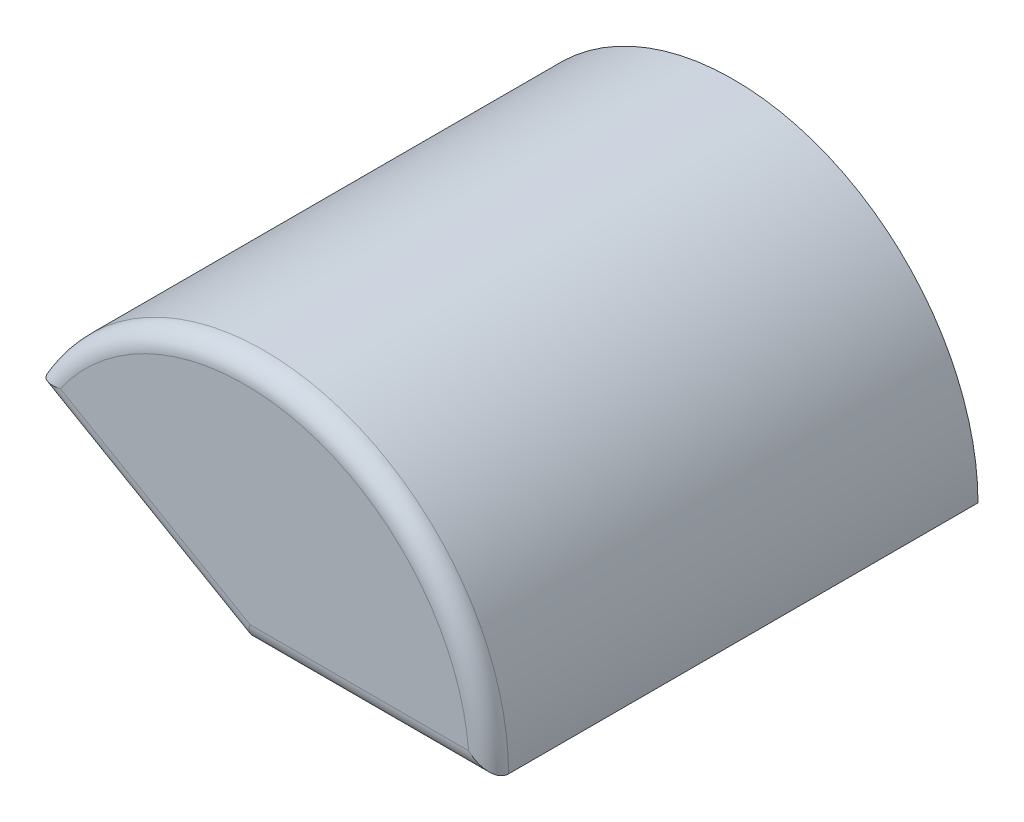
SolidWorks part; units mm, degrees
ref_plane "Front Plane" through (0, 0, 0) normal (0, 0, 1) x (1, 0, 0)
ref_plane "Top Plane" through (0, 0, 0) normal (0, 1, 0) x (1, 0, 0)
ref_plane "Right Plane" through (0, 0, 0) normal (1, 0, 0) x (0, 0, -1)
sketch "Sketch1" plane through (0, 0, 0) normal (0, 0, 1) x (1, 0, 0)
  line L0 (-21.6506, 12.5) -> (0, 0)
  line L1 (0, 0) -> (25, 0)
  arc A0 (25, 0) -> (-21.6506, 12.5) centre (0, 0) ccw
  dimension "D1" = 150
  dimension "D2" = 25
extrude "Boss-Extrude1" add sketch "Sketch1" along normal blind 50
fillet "Fillet1" radius 2 3 edges at (-10.8253, 6.25, 50) (6.4705, 24.1481, 50) (12.5, 0, 50)
equation "\"angle\"=150"
equation "\"thicknes\"=50"
equation "\"diameter\"=25"
equation "\"D1@Sketch1\"= \"angle\""
equation "\"D2@Sketch1\"= \"diameter\""
equation "\"D1@Boss-Extrude1\"= \"thicknes\""
